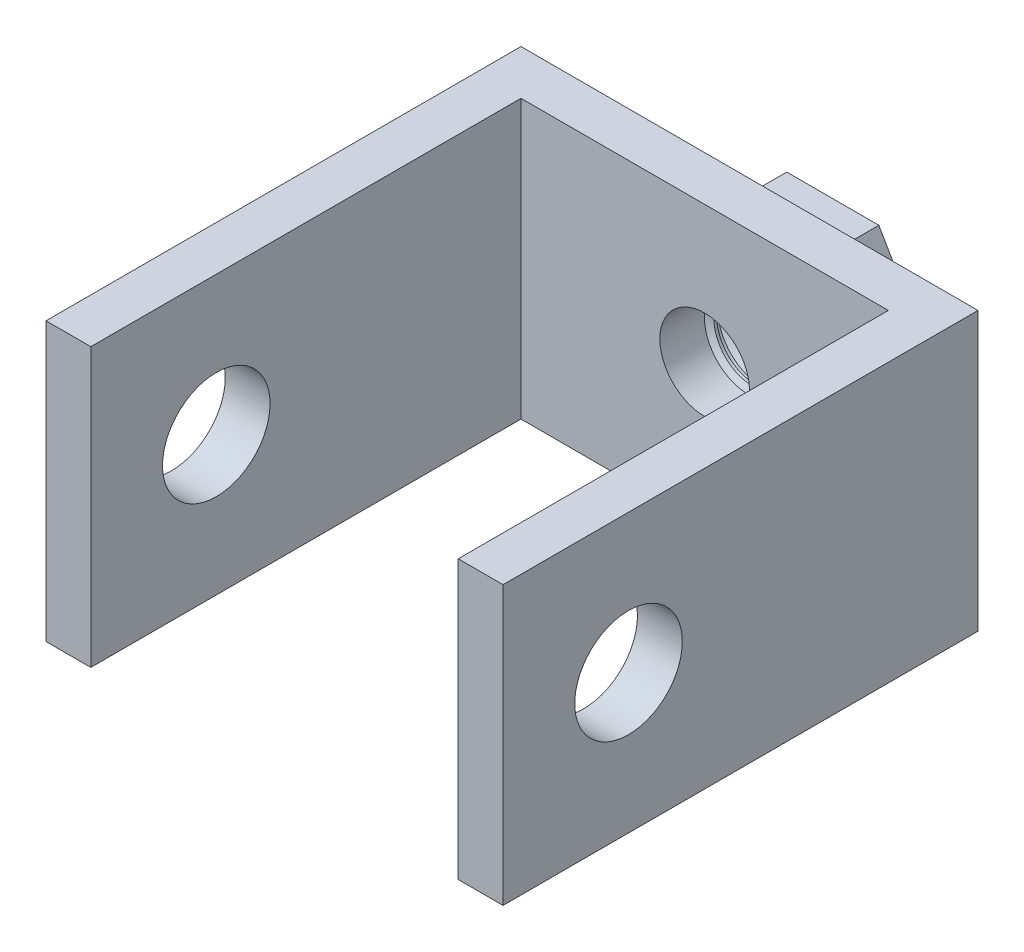
SolidWorks part; units mm, degrees
ref_plane "Front Plane" through (0, 0, 0) normal (0, 0, 1) x (1, 0, 0)
ref_plane "Top Plane" through (0, 0, 0) normal (0, 1, 0) x (1, 0, 0)
ref_plane "Right Plane" through (0, 0, 0) normal (1, 0, 0) x (0, 0, -1)
sketch "Sketch1" plane through (0, 0, 0) normal (0, 1, 0) x (1, 0, 0)
  line L0 (-20.5, 0) -> (20.5, 0)
  line L1 (20.5, 0) -> (20.5, -58)
  line L2 (20.5, -58) -> (25.5, -58)
  line L3 (25.5, -58) -> (25.5, 5)
  line L4 (25.5, 5) -> (-25.5, 5)
  line L5 (-25.5, 5) -> (-25.5, -58)
  line L6 (-25.5, -58) -> (-20.5, -58)
  line L7 (-20.5, -58) -> (-20.5, 0)
  dimension "D1" = 5
  dimension "D2" = 5
  dimension "D3" = 41
  dimension "D4" = 58
extrude "Boss-Extrude1" add sketch "Sketch1" along normal blind 31
hole_wizard "Ø12.0 mm Dowel Holes1" positions "Sketch2" profile "Sketch4" hole size "Ø12.0" standard "ISO" end condition through all
sketch "Sketch2" plane through (25.5, 0, 0) normal (1, 0, 0) x (0, 0, -1)
  line L0 (-58, 31) -> (-58, 0) construction
  line L1 (-58, 31) -> (5, 31) construction
  line L3 (-34, 31) -> (-34, 0) construction
  line L4 (-58, 0) -> (5, 0) construction
  point P0 (-34, 15.5)
  dimension "D1" = 24
sketch "Sketch4" plane through (25.5, 15.5, 34) normal (0, 1, 0) x (0, 0, -1)
  line L0 (0, 0) -> (0, 51)
  line L1 (0, 51) -> (6, 51)
  line L2 (6, 51) -> (6, 0)
  line L5 (6, 0) -> (0, 0)
  line L11 (0, -6.35) -> (0, 107.95) construction
  dimension "Thru Hole Dia." = 12
  dimension "Thru Hole Depth" = 51
hole_wizard "Ø10.0 mm Dowel Holes1" positions "Sketch5" profile "Sketch6" hole size "Ø10.0" standard "ISO" end condition through all
sketch "Sketch5" plane through (0, 0, -5) normal (0, 0, -1) x (-1, 0, 0)
  line L0 (25.5, 0) -> (-25.5, 31) construction
  line L2 (-25.5, 0) -> (25.5, 31) construction
  point P0 (0, 15.5)
sketch "Sketch6" plane through (0, 15.5, -5) normal (1, 0, 0) x (0, 1, 0)
  line L0 (0, 0) -> (0, 63)
  line L1 (0, 63) -> (5, 63)
  line L2 (5, 63) -> (5, 0)
  line L5 (5, 0) -> (0, 0)
  line L11 (0, -6.35) -> (0, 107.95) construction
  dimension "Thru Hole Dia." = 10
  dimension "Thru Hole Depth" = 63
sketch "Sketch7" plane through (0, 0, -5) normal (0, 0, -1) x (-1, 0, 0)
  line L0 (-25.5, 0) -> (25.5, 0) construction
  line L1 (10.2768, 15.5) -> (5.1384, 24.4)
  line L2 (5.1384, 24.4) -> (-5.1384, 24.4)
  line L3 (-5.1384, 24.4) -> (-10.2768, 15.5)
  line L4 (-10.2768, 15.5) -> (-5.1384, 6.6)
  line L5 (-5.1384, 6.6) -> (5.1384, 6.6)
  line L6 (5.1384, 6.6) -> (10.2768, 15.5)
  circle A0 centre (0, 15.5) radius 8.9 construction
  circle A1 centre (0, 15.5) radius 5
  dimension "D1" = 17.8
extrude "Boss-Extrude2" add sketch "Sketch7" along normal blind 9.3
thread "Thread1" pitch 1.25 method extrude profile "Thread Profile1" start angle 0, offset 0, length 9.3, pitch 1.5, diameter 10
ref_plane "Plane1" through (5, 15.5, -14.3) normal (0, -1, 0) x (1, 0, 0)
sketch "Thread Profile1" plane through (5, 15.5, -14.3) normal (0, -1, 0) x (1, 0, 0)
  line L0 (0, 0) -> (0, 1.25) construction
  line L11 (0, 0) -> (0, 1.0937)
  line L12 (0, 1.0937) -> (-0.6766, 0.7031)
  line L13 (-0.6766, 0.7031) -> (-0.6766, 0.3906)
  line L15 (-0.6766, 0.3906) -> (0, 0)
  line L17 (-0.6766, 0.5469) -> (0, 0.5469) construction
  point P2 (0, 0)
  dimension "Pitch" = 1.25
  dimension "Profile_Angle" = 60
  dimension "Profile_Land" = 0.3125
  dimension "Profile_Height" = 0.6766
sketch "Sketch13" plane through (0, 0, 58) normal (0, 0, 1) x (1, 0, 0)
  line L1 (-25.5, 31) -> (25.5, 31)
  line L2 (-25.5, 31) -> (-25.5, 0)
  line L3 (-25.5, 0) -> (25.5, 0)
  line L4 (25.5, 31) -> (25.5, 0)
extrude "Cut-Extrude1" cut sketch "Sketch13" against normal blind 10
